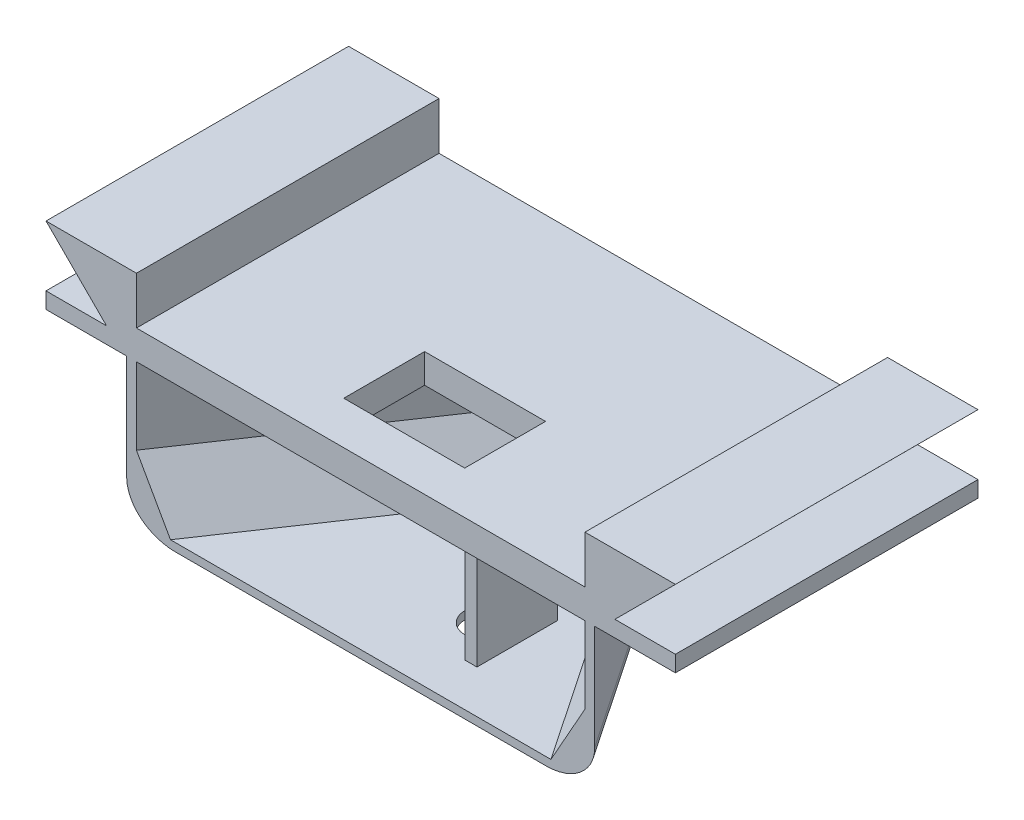
SolidWorks part; units mm, degrees
other "Camera1"
ref_plane "Front Plane" through (0, 0, 0) normal (0, 0, 1) x (1, 0, 0)
ref_plane "Top Plane" through (0, 0, 0) normal (0, 1, 0) x (1, 0, 0)
ref_plane "Right Plane" through (0, 0, 0) normal (1, 0, 0) x (0, 0, -1)
sketch "Sketch1" plane through (0, 0, 0) normal (0, 1, 0) x (1, 0, 0)
  line L0 (0, 0) -> (-116, 0)
  line L1 (-116, 0) -> (-75.5008, 60)
  line L2 (-75.5008, 60) -> (-40.5008, 60)
  line L3 (-40.5008, 60) -> (0, 0)
  dimension "D1" = 60
  dimension "D2" = 116
  dimension "D3" = 35
  dimension "D5" = 72.39
  dimension "D6" = 72.3891
extrude "Boss-Extrude1" add sketch "Sketch1" against normal blind 40
shell "Shell1" thickness 2 removed face at (-58, -20, 0)
sketch "Sketch5" plane through (0, 0, -58) normal (0, 0, 1) x (1, 0, 0)
  line L0 (-41.5637, -2) -> (-74.4378, -2) construction
  line L1 (-53.4928, -23) -> (-61.9928, -23)
  line L2 (-53.4928, -23) -> (-53.4928, -14.5)
  line L3 (-53.4928, -14.5) -> (-61.9928, -14.5)
  line L4 (-61.9928, -23) -> (-61.9928, -14.5)
  line L5 (-74.4378, -38) -> (-74.4378, -2) construction
  line L7 (-41.5637, -38) -> (-41.5637, -2) construction
  dimension "D1" = 12.445
  dimension "D2" = 8.5
  dimension "D3" = 12.5
  dimension "D4" = 11.929
extrude "Cut-Extrude5" cut sketch "Sketch5" against normal blind 6
chamfer "Chamfer3" distance 15 angle 25 2 edges at (-94.0124, -38, -29) (-21.9884, -38, -29) first distance on face at (-94.0124, -20, -29) first distance on face at (-21.9884, -20, -29)
fillet "Fillet1" radius 10 2 edges at (-20.2504, -40, -30) (-95.7504, -40, -30)
fillet "Fillet2" radius 5 5 edges at (-40.5008, -15, -60) (-44.0345, -37.0711, -60) (-75.5008, -15, -60) (-71.9671, -37.0711, -60) (-58.0008, -40, -60)
sketch "Sketch12" plane through (0, -40, 0) normal (0, -1, 0) x (-1, 0, 0)
  circle A0 centre (48.251, 21.2853) radius 5.2
sketch "Sketch13" plane through (0, -2, 0) normal (0, -1, 0) x (1, 0, 0)
  line L1 (-39.8423, -30.6584) -> (-42.8423, -30.6584)
  line L2 (-39.8423, -30.6584) -> (-39.8423, -10.6584)
  line L3 (-39.8423, -10.6584) -> (-42.8423, -10.6584)
  line L4 (-42.8423, -30.6584) -> (-42.8423, -10.6584)
  dimension "D1" = 3
extrude "Boss-Extrude3" add sketch "Sketch13" along normal blind 36
extrude "Cut-Extrude12" cut sketch "Sketch12" against normal blind 9
sketch "Sketch15" plane through (0, 0, 0) normal (0, 1, 0) x (1, 0, 0)
  line L8 (-136, 75) -> (20, 75)
  line L9 (20, 0) -> (20, 75)
  line L10 (20, 0) -> (-136, 0)
  line L11 (-136, 0) -> (-136, 75)
extrude "Boss-Extrude7" add sketch "Sketch15" along normal blind 15
sketch "Sketch16" plane through (0, 0, 0) normal (0, 0, 1) x (1, 0, 0)
  line L8 (20, 15) -> (20, 0)
  line L9 (20, 0) -> (5.0045, 0)
  line L10 (0, 0) -> (20, 0) construction
  line L11 (5.0045, 0) -> (20, 15)
extrude "Cut-Extrude14" cut sketch "Sketch16" against normal blind 75
sketch "Sketch17" plane through (0, 0, 0) normal (0, 0, 1) x (1, 0, 0)
  line L0 (-136, 15) -> (-136, 0)
  line L1 (-136, 0) -> (-121.0045, 0)
  line L2 (-136, 0) -> (-116, 0) construction
  line L3 (-121.0045, 0) -> (-136, 15)
extrude "Cut-Extrude15" cut sketch "Sketch17" against normal blind 75
sketch "Sketch18" plane through (0, 0, 0) normal (0, -1, 0) x (1, 0, 0)
  line L0 (-116, 0) -> (-121.0045, 0)
  line L1 (-121.0045, 0) -> (-136.0045, 0)
  line L2 (-136.0045, 0) -> (-136.0045, -75)
  line L3 (-136.0045, -75) -> (-121.0045, -75)
  line L5 (20.0045, -75) -> (20.0045, 0)
  line L6 (20.0045, 0) -> (-116, 0)
  line L7 (20.0045, -75) -> (5.0045, -75)
  line L8 (-121.0045, -75) -> (5.0045, -75)
extrude "Boss-Extrude8" add sketch "Sketch18" along normal blind 4 contours L8 L7 L5 L6 L0 L1 L2 L3
sketch "Sketch20" plane through (0, -4, 0) normal (0, -1, 0) x (-1, 0, 0)
  line L1 (42.8423, 30.6584) -> (72.8207, 30.6584)
  line L2 (42.8423, 30.6584) -> (42.8423, 10.6218)
  line L3 (42.8423, 10.6218) -> (72.8207, 10.6218)
  line L4 (72.8207, 30.6584) -> (72.8207, 10.6218)
extrude "Cut-Extrude17" cut sketch "Sketch20" against normal blind 39 contours L2 L1 L4 L3
sketch "Sketch21" plane through (0, 0, 0) normal (0, 0, 1) x (1, 0, 0)
  line L6 (-136, 15) -> (20, 15) construction
  line L7 (-2.413, 15) -> (-113.583, 15)
  line L9 (-2.413, 15) -> (-113.583, 15)
  line L11 (-2.413, 15) -> (-2.413, 3.2309)
  line L12 (-2.413, 3.2309) -> (-113.583, 3.2309)
  line L13 (-113.583, 15) -> (-113.583, 3.2309)
extrude "Cut-Extrude18" cut sketch "Sketch21" against normal blind 80 contours L11 L9 L13 L12
